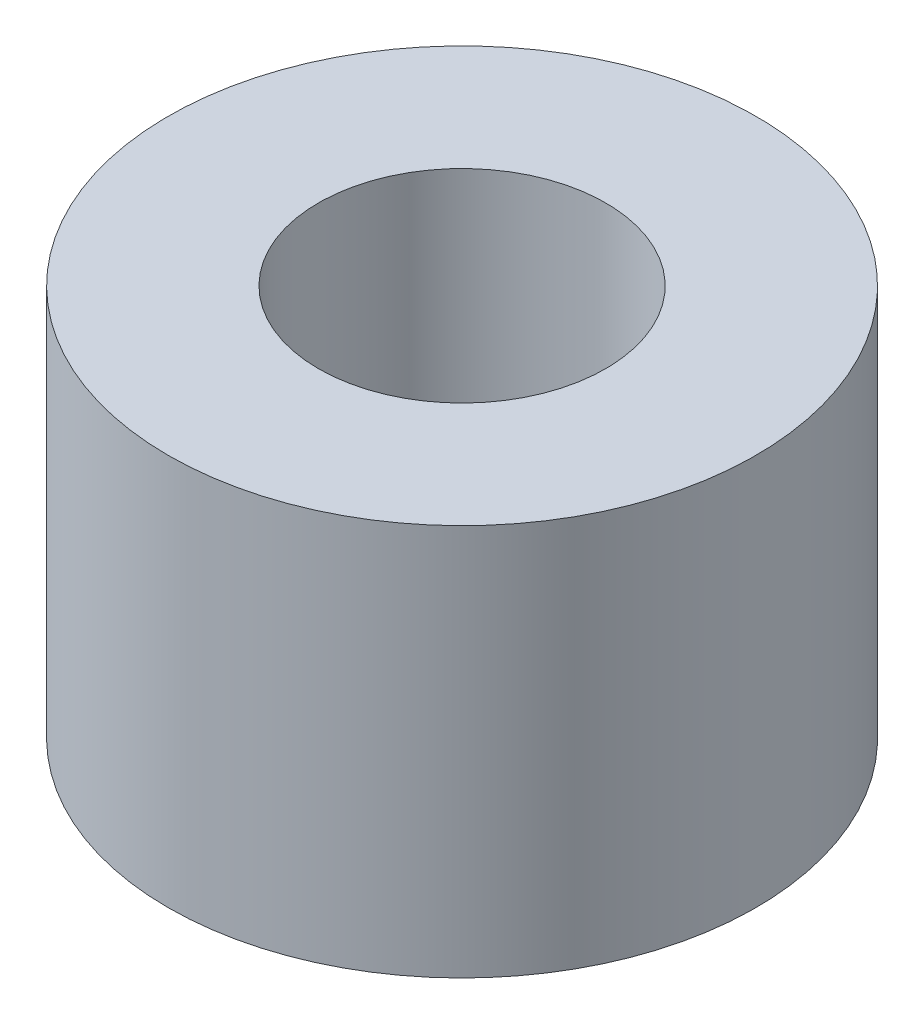
SolidWorks part; units mm, degrees
ref_plane "Front Plane" through (0, 0, 0) normal (0, 0, 1) x (1, 0, 0)
ref_plane "Top Plane" through (0, 0, 0) normal (0, 1, 0) x (1, 0, 0)
ref_plane "Right Plane" through (0, 0, 0) normal (1, 0, 0) x (0, 0, -1)
sketch "Sketch1" plane through (0, 0, 0) normal (0, 1, 0) x (1, 0, 0)
  circle A0 centre (0, 0) radius 2.25
  circle A1 centre (0, 0) radius 1.1
  dimension "D1" = 2.2
  dimension "D2" = 4.5
extrude "Boss-Extrude1" add sketch "Sketch1" along normal blind 3
